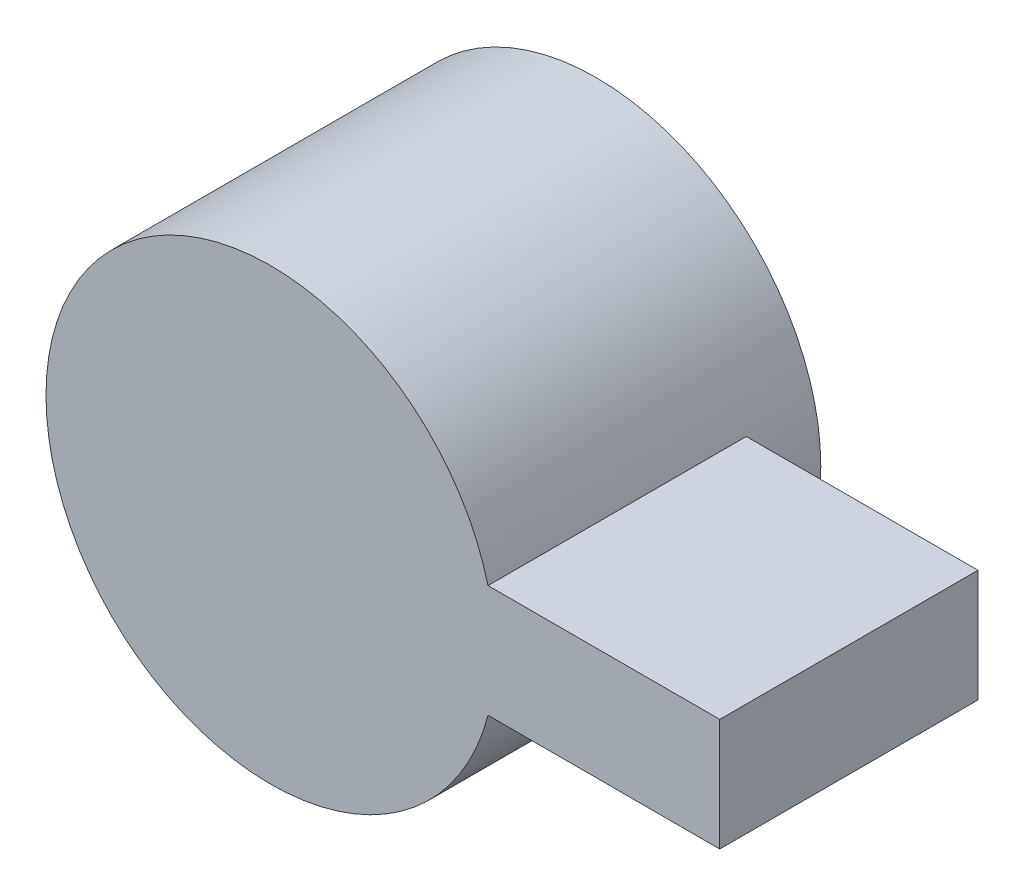
SolidWorks part; units mm, degrees
other "Uwaga1"
sketch "Szkic3" plane through (-10, 10, 11.5) normal (-0.4582, 0.8713, 0.1758) x (-0.8726, -0.4786, 0.0973)
ref_plane "Płaszczyzna przednia" through (0, 0, 0) normal (0, 0, 1) x (1, 0, 0)
ref_plane "Płaszczyzna górna" through (0, 0, 0) normal (0, 1, 0) x (1, 0, 0)
ref_plane "Płaszczyzna prawa" through (0, 0, 0) normal (1, 0, 0) x (0, 0, -1)
sketch "Szkic1" plane through (0, 0, 0) normal (0, 0, 1) x (1, 0, 0)
  line L0 (1.55, 2.6268) -> (1.55, -2.6268)
  line L1 (0, 0) -> (33.7661, 0) construction
  line L2 (10, 2.5) -> (20, 2.5)
  line L4 (10, -2.5) -> (20, -2.5)
  line L5 (20, 2.5) -> (20, -2.5)
  line L6 (10, -2.5) -> (9.6825, -2.5)
  line L7 (10, 2.5) -> (9.6825, 2.5)
  circle A0 centre (0, 0) radius 3.05
  circle A1 centre (0, 0) radius 10
  point P5 (-3.05, 0)
  point P11 (20, 0)
  dimension "D1" = 6.1
  dimension "D2" = 4.6
  dimension "D3" = 20
  dimension "D4" = 5
  dimension "D5" = 10
  dimension "D6" = 0.3175
extrude "Dodanie-wyciągnięcie3" add sketch "Szkic1" along normal blind 11.5 contours L1 A1 L6 L4 L5 | A1 L1 L5 L2 L7 | A0 A1 | L0 A0 | L1 L0 A0 | L0 L1 A0 region at (2.1648, 1.0279, 0) region at (9.6397, -1.2244, 0) region at (14.947, 1.2565, 0) region at (14.947, -1.2565, 0) region at (-0.5111, 0, 0) region at (2.1648, -1.0279, 0)
extrude "Wytnij-wyciągnięcie1" cut sketch "Szkic1<6>" along normal blind 10 contours L0 A0 region at (-0.5111, 0, 0)
sketch "Szkic1<6>" plane through (0, 0, 0) normal (0, 0, 1) x (1, 0, 0) same geometry as "Szkic1"
sketch "Szkic2" plane through (0, 0, 0) normal (0, 0, -1) x (-1, 0, 0)
  line L5 (-1.55, 2.6268) -> (-1.55, -2.6268) construction
  line L11 (-1.55, 2.6268) -> (-1.55, -2.6268)
  circle A1 centre (0, 0) radius 10
  circle A2 centre (0, 0) radius 10
  circle A3 centre (0, 0) radius 3.05
  circle A4 centre (0, 0) radius 3.05
  arc M6 (-9.6825, -2.5) -> (-9.6825, 2.5) centre (0, 0) ccw
  arc M7 (-1.55, 2.6268) -> (-1.55, -2.6268) centre (0, 0) cw
  dimension "D1" = 0
  dimension "D2" = 0
extrude "Dodanie-wyciągnięcie4" add sketch "Szkic2" along normal blind 3 contours A2 A4 M6 M7 region at (-1.2244, -9.6397, 0)
